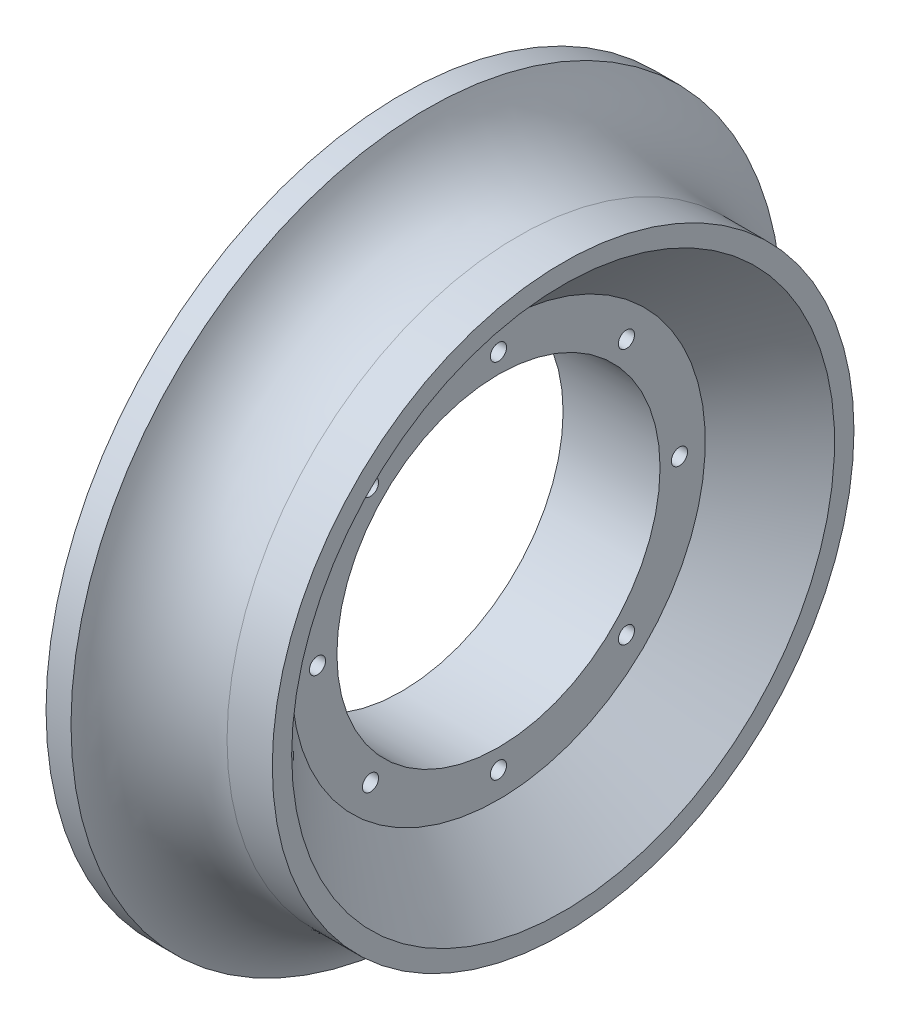
SolidWorks part; units mm, degrees
material "ABS"
ref_plane "Płaszczyzna przednia" through (0, 0, 0) normal (0, 0, 1) x (1, 0, 0)
ref_plane "Płaszczyzna górna" through (0, 0, 0) normal (0, 1, 0) x (1, 0, 0)
ref_plane "Płaszczyzna prawa" through (0, 0, 0) normal (1, 0, 0) x (0, 0, -1)
sketch "Szkic1" plane through (0, 0, 0) normal (0, 0, 1) x (1, 0, 0)
  line L0 (0, 0) -> (62.2258, 0) construction
  line L83 (50, 90) -> (50, 84)
  line L84 (0, 50) -> (30, 50)
  line L85 (36, 90) -> (50, 90)
  line L86 (50, 84) -> (30, 64)
  line L87 (30, 50) -> (30, 64)
  line L88 (0, 110) -> (0, 50)
  line L89 (0, 110) -> (7.7157, 110)
  arc A27 (7.7157, 110) -> (36, 90) centre (36, 120) ccw
revolve "Obrót1" add sketch "Szkic1" angle 360 about L0
sketch "Szkic2" plane through (0, 0, 0) normal (-1, 0, 0) x (0, 0, 1)
  circle A0 centre (0, 56) radius 2.5
  circle A1 centre (39.598, 39.598) radius 2.5
  circle A2 centre (56, 0) radius 2.5
  circle A3 centre (39.598, -39.598) radius 2.5
  circle A4 centre (0, -56) radius 2.5
  circle A5 centre (-39.598, -39.598) radius 2.5
  circle A6 centre (-56, 0) radius 2.5
  circle A7 centre (-39.598, 39.598) radius 2.5
  point P20 (0, 0)
  dimension "D1" = 5
  dimension "D2" = 56
  dimension "D3" = 8
extrude "Wytnij-wyciągnięcie1" cut sketch "Szkic2" against normal through all
